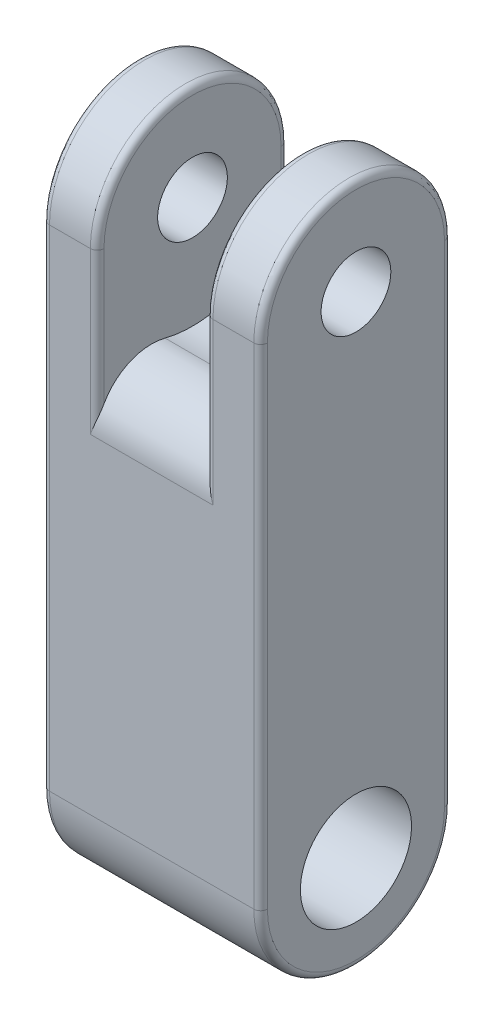
SolidWorks part; units mm, degrees
ref_plane "Front Plane" through (0, 0, 0) normal (0, 0, 1) x (1, 0, 0)
ref_plane "Top Plane" through (0, 0, 0) normal (0, 1, 0) x (1, 0, 0)
ref_plane "Right Plane" through (0, 0, 0) normal (1, 0, 0) x (0, 0, -1)
sketch "Sketch1" plane through (0, 0, 0) normal (1, 0, 0) x (0, 0, -1)
  line L0 (-5.5562, 0) -> (-5.5562, 28.575)
  line L1 (5.5562, 28.575) -> (5.5563, 0)
  arc A0 (-5.5562, 0) -> (5.5563, 0) centre (0, 0) ccw
  arc A1 (-5.5562, 28.575) -> (5.5562, 28.575) centre (0, 28.575) cw
  circle A2 centre (0, 0) radius 3.2385
  circle A3 centre (0, 28.575) radius 2.032
  dimension "D1" = 5.5562
  dimension "D2" = 6.477
  dimension "D4" = 4.064
  dimension "D3" = 28.575
extrude "Boss-Extrude1" add sketch "Sketch1" along normal mid plane 12.7
sketch "Sketch2" plane through (0, 0, 0) normal (1, 0, 0) x (0, 0, -1)
  circle A0 centre (0, 28.575) radius 6.5
  dimension "D1" = 13
extrude "Cut-Extrude1" cut sketch "Sketch2" against normal mid plane 6.35
fillet "Fillet1" radius 3.175 2 edges at (0, 25.2019, 5.5562) (0, 25.2019, -5.5562)
fillet "Fillet2" radius 0.3969 14 edges at (6.35, 14.2875, -5.5563) (6.35, -5.5562, 0) (6.35, 14.2875, 5.5562) (-6.35, 14.2875, -5.5563) (-6.35, -5.5562, 0) (-6.35, 14.2875, 5.5562) (6.35, 34.1313, 0) (-6.35, 34.1313, 0) (-3.175, 23.8863, -5.5562) (-3.175, 23.8863, 5.5562) (3.175, 23.8863, -5.5562) (3.175, 23.8863, 5.5562) (-3.175, 34.1313, 0) (3.175, 34.1313, 0)
